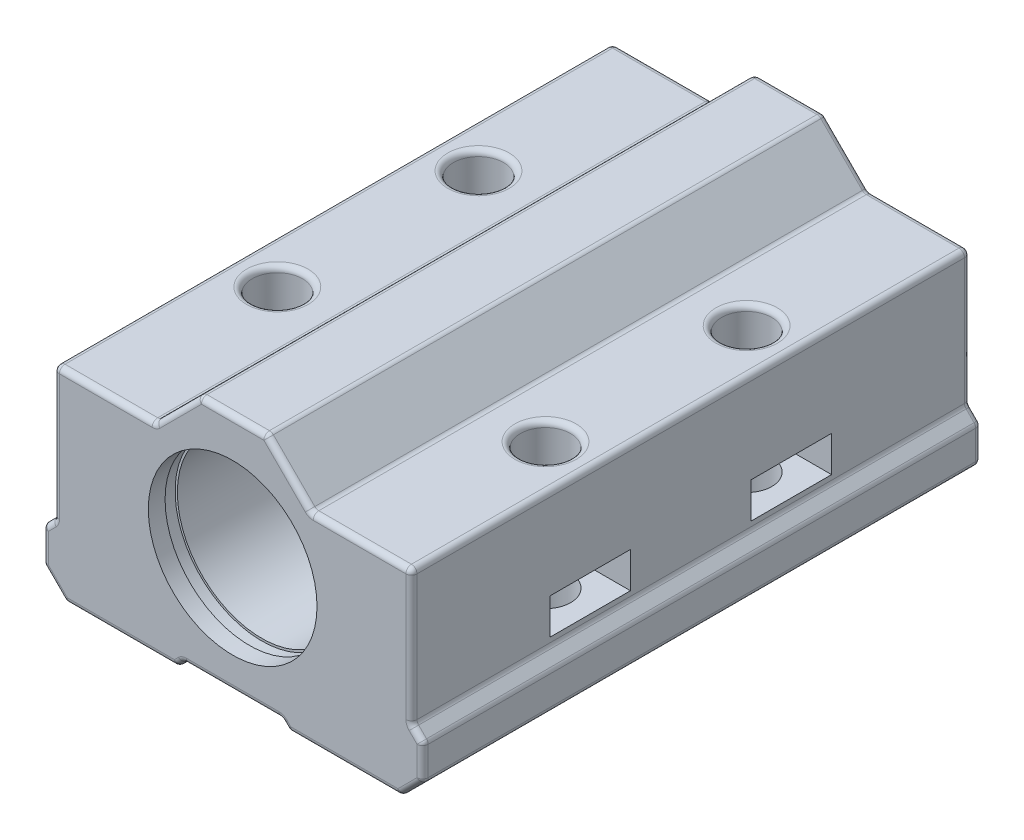
SolidWorks part; units mm, degrees
other "Camera1"
material "1060 Alloy"
ref_plane "Front Plane" through (0, 0, 0) normal (0, 0, 1) x (1, 0, 0)
ref_plane "Top Plane" through (0, 0, 0) normal (0, 1, 0) x (1, 0, 0)
ref_plane "Right Plane" through (0, 0, 0) normal (1, 0, 0) x (0, 0, -1)
sketch "Sketch1" plane through (0, 0, 0) normal (0, 0, 1) x (1, 0, 0)
  line L0 (-7, 0) -> (-7, 7) construction
  line L1 (-17, -11) -> (-4, -11)
  line L2 (-17, -11) -> (-17, -5)
  line L3 (-3, 11) -> (3, 11)
  line L4 (17, -11) -> (17, -5)
  line L5 (-17, -11) -> (10.8182, 7) construction
  line L6 (-10.8182, 7) -> (17, -11) construction
  line L7 (-7, 7) -> (7, 7) construction
  line L8 (7, 7) -> (7, 0) construction
  line L9 (-7, 7) -> (-16.0014, 7)
  line L10 (-16.0014, 7) -> (-7, 7)
  line L11 (7, 7) -> (16, 7)
  line L12 (-7, 7) -> (-3, 11)
  line L13 (7, 7) -> (3, 11)
  line L14 (0, 0) -> (0, -11) construction
  line L15 (17, 7) -> (16, 7) construction
  line L16 (-16.0014, -11) -> (-16.0014, -5) construction
  line L17 (-16.0014, -5) -> (-17, -5)
  line L18 (-17, -5) -> (-17, -11)
  line L19 (-16.0014, 7) -> (-16.0014, -5)
  line L20 (16, 7) -> (16, -5) construction
  line L21 (16, -10.3529) -> (16, -11)
  line L22 (16, -11) -> (16, -10.3529)
  line L23 (17, -5) -> (16, -5)
  line L24 (16, 7) -> (16, -5)
  line L25 (0, -11) -> (0, -10.3529) construction
  line L26 (-4, -10.3529) -> (4, -10.3529)
  line L27 (4, -10.3529) -> (4, -11)
  line L29 (-4, -11) -> (-4, -10.3529)
  line L30 (4, -11) -> (17, -11)
  circle A0 centre (0, 0) radius 4
  circle A1 centre (0, 0) radius 7 construction
  point P6 (0, 0)
  point P30 (0, -10.3529)
  dimension "D1" = 18
  dimension "D2" = 10
  dimension "D3" = 34
  dimension "D4" = 11
extrude "Boss-Extrude1" add sketch "Sketch1" along normal blind 50 contours L24 L11 L13 L3 L12 L9 L19 L17 L2 L1 L4 L23 A0 region at (-16.595, -8, 0)
chamfer "Chamfer1" distance 2 angle 45 2 edges at (-17, -11, 25) (17, -11, 25)
chamfer "Chamfer2" distance 1 angle 45 4 edges at (17, -5, 25) (-17, -5, 25) (-4, -11, 25) (4, -11, 25)
fillet "Fillet1" radius 0.5 56 edges at (15, -11, 25) (5, -11, 25) (-4.3529, -10.3529, 25) (4.3529, -10.3529, 25) (-17, -9, 25) (-17, -6, 25) (-15, -11, 25) (-5, -11, 25) (4, 0, 0) (5, 9, 0) (-5, 9, 0) (-16.5007, -5.5007, 0) (-17, -7.5, 0) (-16, -10, 0) (-10, -11, 0) (-4.6765, -10.6765, 0) (0, -10.3529, 0) (4.6765, -10.6765, 0) (10, -11, 0) (16, -10, 0) (16.5, -5.5, 0) (17, -9, 25) (17, -6, 25) (17, -7.5, 0) (16, -5, 25) (16, 1, 0) (16, 7, 25) (7, 7, 25) (11.5, 7, 0) (4, 0, 50) (16, -10, 50) (10, -11, 50) (4.6765, -10.6765, 50) (0, -10.3529, 50) (-4.6765, -10.6765, 50) (-10, -11, 50) (-16, -10, 50) (-17, -7.5, 50) (-16.5007, -5.5007, 50) (-5, 9, 50) (5, 9, 50) (11.5, 7, 50) (16, 1, 50) (16.5, -5.5, 50) (17, -7.5, 50) (3, 11, 25) (0, 11, 50) (-3, 11, 25) (0, 11, 0) (-7, 7, 25) (-11.5007, 7, 50) (-11.5007, 7, 0) (-16.0014, 7, 25) (-16.0014, 0.9993, 50) (-16.0014, -5.0014, 25) (-16.0014, 0.9993, 0)
sketch "Sketch2" plane through (0, 0, 0) normal (0, 0, -1) x (-1, 0, 0)
  circle A0 centre (0, 0) radius 7
  circle A1 centre (0, 0) radius 3
extrude "Cut-Extrude1" cut sketch "Sketch2" against normal blind 0.5
sketch "Sketch3" plane through (0, 0, 50) normal (0, 0, 1) x (1, 0, 0)
  circle A0 centre (0, 0) radius 7.55
  dimension "D1" = 15.1
sketch "Sketch4" plane through (0, -11, 0) normal (0, -1, 0) x (1, 0, 0)
  line L0 (14.7929, 0.5) -> (-14.7929, 49.5) construction
  line L2 (12, 34) -> (-12, 34) construction
  line L3 (12, 34) -> (12, 16) construction
  line L4 (12, 16) -> (-12, 16) construction
  line L5 (-12, 34) -> (-12, 16) construction
  line L6 (12, 34) -> (-12, 16) construction
  line L7 (12, 16) -> (-12, 34) construction
  circle A0 centre (-12, 16) radius 2.25
  circle A1 centre (12, 16) radius 2.25
  circle A2 centre (12, 34) radius 2.25
  circle A3 centre (-12, 34) radius 2.25
  point P4 (0, 25)
  dimension "D1" = 24
  dimension "D3" = 4.5
  dimension "D4" = 4.5
  dimension "D2" = 18
extrude "Cut-Extrude3" cut sketch "Sketch4" against normal blind 30
fillet "Fillet5" radius 0.5 8 edges at (12, -11, 13.75) (12, -11, 31.75) (-12, -11, 13.75) (-12, -11, 31.75) (12, 7, 36.25) (12, 7, 18.25) (-12, 7, 13.75) (-12, 7, 31.75)
extrude "Cut-Extrude4" cut sketch "Sketch3" against normal up to next
sketch "Sketch5" plane through (0, 0, 0) normal (0, 0, -1) x (-1, 0, 0)
  circle A0 centre (0, 0) radius 7.75
  dimension "D1" = 15.5
extrude "Cut-Extrude5" cut sketch "Sketch5" against normal blind 1.1 from offset 1.3 offset against normal yes
sketch "Sketch6" plane through (0, 0, 50) normal (0, 0, 1) x (1, 0, 0)
  circle A0 centre (0, 0) radius 7.75
  dimension "D1" = 15.5
extrude "Cut-Extrude6" cut sketch "Sketch6" against normal blind 1.1 from offset 1.5 offset against normal yes
sketch "Sketch7" plane through (16, 0, 0) normal (1, 0, 0) x (0, 0, -1)
  line L0 (-34, -10.5) -> (-34, 6.5) construction
  line L1 (-19.6, -4.3565) -> (-12.4, -4.3565)
  line L2 (-19.6, -4.3565) -> (-19.6, -1.1565)
  line L3 (-19.6, -1.1565) -> (-12.4, -1.1565)
  line L4 (-12.4, -4.3565) -> (-12.4, -1.1565)
  line L5 (-16, -10.5) -> (-16, 6.5) construction
  line L6 (-18.25, -10.5) -> (-13.75, -10.5) construction
  line L7 (-0.5, 6.5) -> (-49.5, 6.5) construction
  line L8 (-0.5, -2.7565) -> (-50.4868, -2.7565) construction
  line L9 (-0.5, -4.7929) -> (-0.5, 6.5) construction
  line L10 (-30.4, -4.3565) -> (-37.6, -4.3565)
  line L11 (-30.4, -4.3565) -> (-30.4, -1.1565)
  line L12 (-30.4, -1.1565) -> (-37.6, -1.1565)
  line L13 (-37.6, -4.3565) -> (-37.6, -1.1565)
  line L14 (-36.25, -10.5) -> (-31.75, -10.5) construction
  point P6 (-16, -1.1565)
  point P15 (-12.4, -2.7565)
  point P24 (-34, -4.3565)
  dimension "D1" = 7.2
  dimension "D2" = 3.2
  dimension "D3" = 7.2
extrude "Cut-Extrude7" cut sketch "Sketch7" against normal up to next
sketch "Sketch8" plane through (-16.0014, 0, 0) normal (-1, 0, 0) x (0, 0, 1)
  line L1 (12.4, -1.1565) -> (19.6, -1.1565)
  line L2 (12.4, -1.1565) -> (12.4, -4.3565)
  line L3 (12.4, -4.3565) -> (19.6, -4.3565)
  line L4 (19.6, -1.1565) -> (19.6, -4.3565)
  line L5 (30.4, -1.1565) -> (37.6, -1.1565)
  line L6 (30.4, -1.1565) -> (30.4, -4.3565)
  line L7 (30.4, -4.3565) -> (37.6, -4.3565)
  line L8 (37.6, -1.1565) -> (37.6, -4.3565)
extrude "Cut-Extrude8" cut sketch "Sketch8" against normal up to next
sketch "Sketch9" plane through (0, 0, 0) normal (0, 0, -1) x (-1, 0, 0)
  circle A0 centre (0, 0) radius 7.55
  circle A1 centre (0, 0) radius 6.75
  dimension "D1" = 0.8
extrude "Boss-Extrude2" add sketch "Sketch9" against normal blind 2 from offset 19.7 offset against normal yes
sketch "Sketch10" plane through (0, 0, 50) normal (0, 0, 1) x (1, 0, 0)
  circle A0 centre (0, 0) radius 7.55
  circle A1 centre (0, 0) radius 6.75
  dimension "D1" = 0.8
extrude "Boss-Extrude3" add sketch "Sketch10" against normal up to surface (8.6 mm away) from offset 19.7 up to face at (-6.75, 0, 21.7)
